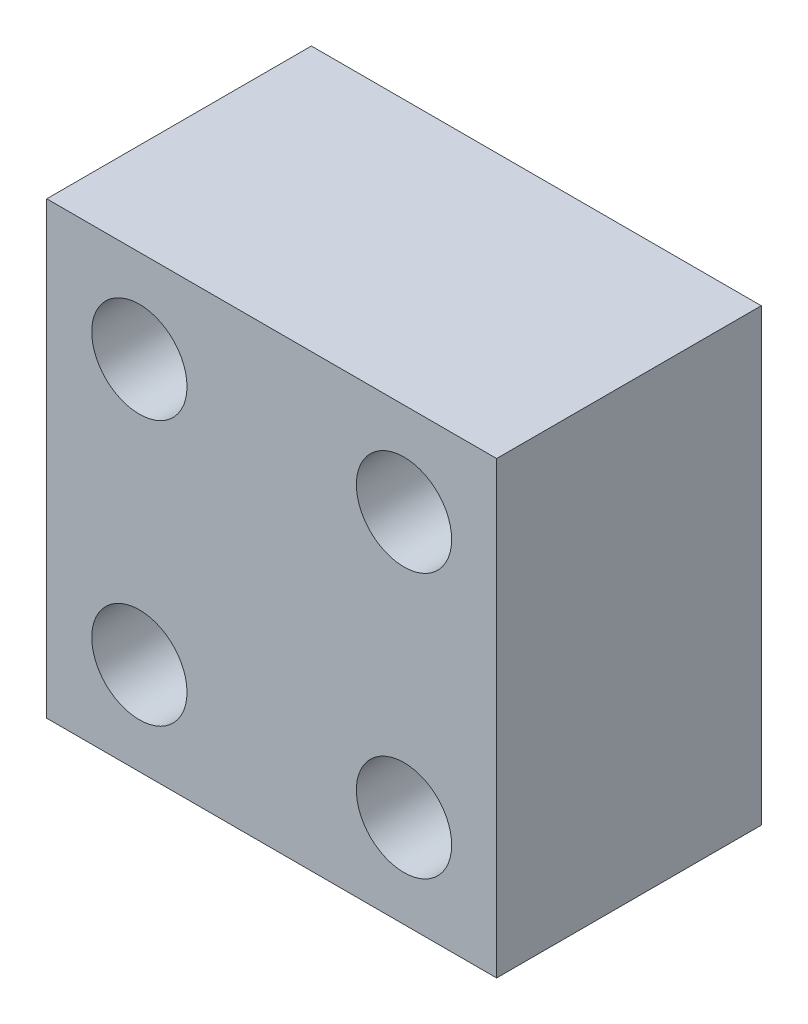
SolidWorks part; units mm, degrees
ref_plane "Front Plane" through (0, 0, 0) normal (0, 0, 1) x (1, 0, 0)
ref_plane "Top Plane" through (0, 0, 0) normal (0, 1, 0) x (1, 0, 0)
ref_plane "Right Plane" through (0, 0, 0) normal (1, 0, 0) x (0, 0, -1)
sketch "Sketch1" plane through (0, 0, 0) normal (0, 0, 1) x (1, 0, 0)
  line L0 (169, 103.999) -> (152, 103.999)
  line L1 (152, 86.999) -> (152, 112.099) construction
  line L2 (152, 86.999) -> (169, 86.999) construction
  line L3 (169, 86.999) -> (169, 112.099) construction
  line L8 (169, 86.999) -> (169, 103.999)
  line L10 (152, 103.999) -> (152, 86.999)
  line L11 (152, 86.999) -> (169, 86.999)
  point P1 (151, 88.462)
  point P7 (167.0836, 86.999)
  point P10 (169, 86.999)
  point P12 (169, 104.999)
  point P15 (151, 105.499)
  dimension "D2" = 17
extrude "Boss-Extrude1" add sketch "Sketch1" along normal blind 10
sketch "Sketch2" plane through (0, 0, 10) normal (0, 0, 1) x (1, 0, 0)
  point P12 (155.5, 100.499)
  point P15 (155.5, 90.499)
  point P18 (165.5, 90.499)
  point P21 (165.5, 100.499)
hole_wizard "M3 Clearance Hole1" positions "Sketch2" profile "Sketch3" hole size "M3" standard "ANSI Metric" end condition through all
sketch "Sketch3" plane through (155.5, 100.499, 10) normal (1, 0, 0) x (0, -1, 0)
  line L0 (0, 0) -> (0, 10)
  line L1 (0, 10) -> (1.8, 10)
  line L2 (1.8, 10) -> (1.8, 0)
  line L5 (1.8, 0) -> (0, 0)
  line L11 (0, -6.35) -> (0, 107.95) construction
  dimension "Thru Hole Dia." = 3.6
  dimension "Thru Hole Depth" = 10
